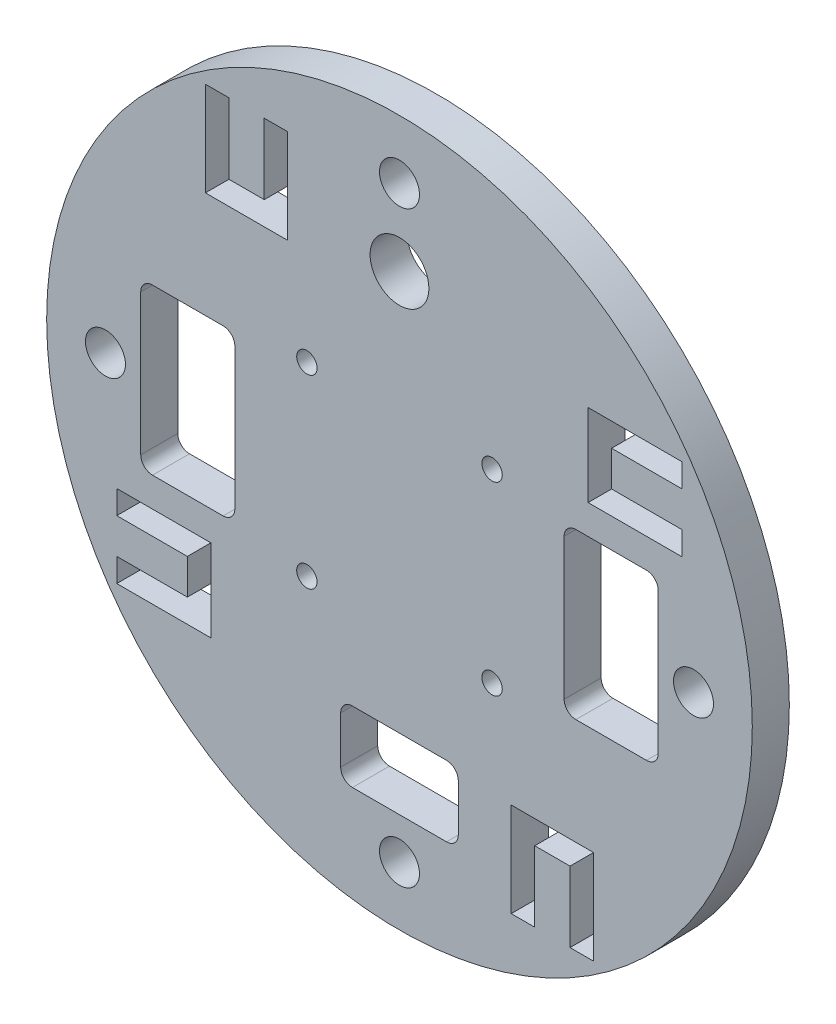
SolidWorks part; units mm, degrees
material "Hexcel AS4C (3000 Filaments)"
ref_plane "Front Plane" through (0, 0, 0) normal (0, 0, 1) x (1, 0, 0)
ref_plane "Top Plane" through (0, 0, 0) normal (0, 1, 0) x (1, 0, 0)
ref_plane "Right Plane" through (0, 0, 0) normal (1, 0, 0) x (0, 0, -1)
sketch "Sketch1" plane through (0, 0, 0) normal (0, 0, 1) x (1, 0, 0)
  circle A0 centre (0, 0) radius 38.1
  dimension "D1" = 76.2
extrude "Boss-Extrude1" add sketch "Sketch1" along normal blind 4 contours A0
sketch "Sketch2" plane through (0, 0, 4) normal (0, 0, 1) x (1, 0, 0)
  circle A0 centre (10, 10) radius 1.1
  circle A1 centre (10, -10) radius 1.1
  circle A2 centre (-10, -10) radius 1.1
  circle A3 centre (-10, 10) radius 1.1
  point P12 (0, 0)
  point P21 (0, 0)
  dimension "D3" = 2.2
  dimension "D1" = 10
  dimension "D2" = 10
  dimension "D4" = 4
extrude "Cut-Extrude1" cut sketch "Sketch2" against normal through all
sketch "Sketch3" plane through (0, 0, 4) normal (0, 0, 1) x (1, 0, 0)
  circle A0 centre (0, -31.75) radius 2.159
  circle A1 centre (-31.75, 0) radius 2.159
  circle A2 centre (0, 31.75) radius 2.159
  circle A3 centre (31.75, 0) radius 2.159
  point P9 (0, 0)
  dimension "D2" = 4.318
  dimension "D1" = 31.75
  dimension "D3" = 4
extrude "Cut-Extrude2" cut sketch "Sketch3" against normal through all both and the other way through all
sketch "Sketch4" plane through (0, 0, 4) normal (0, 0, 1) x (1, 0, 0)
  line L0 (-19.05, -8.89) -> (-26.67, -8.89)
  line L1 (19.05, 8.89) -> (26.67, 8.89)
  line L2 (17.78, 7.62) -> (17.78, -7.62)
  line L3 (19.05, -8.89) -> (26.67, -8.89)
  line L4 (27.94, 7.62) -> (27.94, -7.62)
  line L5 (-17.78, -7.62) -> (-17.78, 7.62)
  line L6 (-19.05, 8.89) -> (-26.67, 8.89)
  line L7 (-27.94, -7.62) -> (-27.94, 7.62)
  arc A0 (17.78, -7.62) -> (19.05, -8.89) centre (19.05, -7.62) ccw
  arc A1 (26.67, -8.89) -> (27.94, -7.62) centre (26.67, -7.62) ccw
  arc A2 (26.67, 8.89) -> (27.94, 7.62) centre (26.67, 7.62) cw
  arc A3 (19.05, 8.89) -> (17.78, 7.62) centre (19.05, 7.62) ccw
  arc A4 (-17.78, 7.62) -> (-19.05, 8.89) centre (-19.05, 7.62) ccw
  arc A5 (-26.67, 8.89) -> (-27.94, 7.62) centre (-26.67, 7.62) ccw
  arc A6 (-26.67, -8.89) -> (-27.94, -7.62) centre (-26.67, -7.62) cw
  arc A7 (-19.05, -8.89) -> (-17.78, -7.62) centre (-19.05, -7.62) ccw
  point P4 (17.78, 0)
  point P8 (17.78, -8.89)
  point P15 (17.78, 8.89)
  point P30 (0, 0)
  point P32 (-17.78, 0)
  dimension "D4" = 1.27
  dimension "D1" = 10.16
  dimension "D2" = 17.78
  dimension "D3" = 17.78
  dimension "D5" = 2
extrude "Cut-Extrude3" cut sketch "Sketch4" against normal through all both and the other way through all
sketch "Sketch5" plane through (0, 0, 4) normal (0, 0, 1) x (1, 0, 0)
  line L0 (0, 23.495) -> (0, -23.495) construction
  line L2 (-5.08, -27.305) -> (5.08, -27.305)
  line L3 (-6.35, -26.035) -> (-6.35, -20.955)
  line L4 (-5.08, -19.685) -> (5.08, -19.685)
  line L5 (6.35, -26.035) -> (6.35, -20.955)
  line L6 (-6.35, -27.305) -> (6.35, -19.685) construction
  line L7 (-6.35, -19.685) -> (6.35, -27.305) construction
  circle A0 centre (0, 23.495) radius 3.175
  arc A1 (-6.35, -20.955) -> (-5.08, -19.685) centre (-5.08, -20.955) cw
  arc A2 (-5.08, -27.305) -> (-6.35, -26.035) centre (-5.08, -26.035) cw
  arc A3 (5.08, -27.305) -> (6.35, -26.035) centre (5.08, -26.035) ccw
  arc A4 (5.08, -19.685) -> (6.35, -20.955) centre (5.08, -20.955) cw
  point P4 (0, 0)
  dimension "D2" = 6.35
  dimension "D5" = 1.27
  dimension "D1" = 46.99
  dimension "D3" = 12.7
  dimension "D4" = 7.62
extrude "Cut-Extrude4" cut sketch "Sketch5" against normal up to next
sketch "Sketch6" plane through (0, 0, 4) normal (0, 0, 1) x (1, 0, 0)
  line L1 (-19.05, 38.147) -> (-13.97, 38.147) construction
  line L2 (-19.05, 38.147) -> (-19.05, 30.527) construction
  line L3 (-19.05, 30.527) -> (-13.97, 30.527) construction
  line L4 (-13.97, 38.147) -> (-13.97, 30.527) construction
  line L5 (-19.05, 38.147) -> (-13.97, 30.527) construction
  line L6 (-19.05, 30.527) -> (-13.97, 38.147) construction
  line L8 (-18.415, 22.907) -> (-14.605, 22.907)
  line L11 (-12.065, 30.527) -> (-12.065, 20.367)
  line L12 (-12.065, 20.367) -> (-20.955, 20.367)
  line L13 (-20.955, 20.367) -> (-20.955, 30.527)
  line L14 (-18.415, 22.907) -> (-18.415, 30.527)
  line L15 (-18.415, 30.527) -> (-20.955, 30.527)
  line L16 (-14.605, 22.907) -> (-14.605, 30.527)
  line L17 (-14.605, 30.527) -> (-12.065, 30.527)
  line L18 (22.907, 18.415) -> (22.907, 14.605)
  line L19 (30.527, 12.065) -> (20.367, 12.065)
  line L20 (20.367, 12.065) -> (20.367, 20.955)
  line L21 (20.367, 20.955) -> (30.527, 20.955)
  line L22 (22.907, 18.415) -> (30.527, 18.415)
  line L23 (30.527, 18.415) -> (30.527, 20.955)
  line L24 (22.907, 14.605) -> (30.527, 14.605)
  line L25 (30.527, 14.605) -> (30.527, 12.065)
  line L26 (38.147, 19.05) -> (38.147, 13.97) construction
  line L27 (38.147, 19.05) -> (30.527, 19.05) construction
  line L28 (30.527, 19.05) -> (30.527, 13.97) construction
  line L29 (38.147, 13.97) -> (30.527, 13.97) construction
  line L30 (38.147, 19.05) -> (30.527, 13.97) construction
  line L31 (30.527, 19.05) -> (38.147, 13.97) construction
  line L32 (18.415, -22.907) -> (14.605, -22.907)
  line L33 (12.065, -30.527) -> (12.065, -20.367)
  line L34 (12.065, -20.367) -> (20.955, -20.367)
  line L35 (20.955, -20.367) -> (20.955, -30.527)
  line L36 (18.415, -22.907) -> (18.415, -30.527)
  line L37 (18.415, -30.527) -> (20.955, -30.527)
  line L38 (14.605, -22.907) -> (14.605, -30.527)
  line L39 (14.605, -30.527) -> (12.065, -30.527)
  line L40 (19.05, -38.147) -> (13.97, -38.147) construction
  line L41 (19.05, -38.147) -> (19.05, -30.527) construction
  line L42 (19.05, -30.527) -> (13.97, -30.527) construction
  line L43 (13.97, -38.147) -> (13.97, -30.527) construction
  line L44 (19.05, -38.147) -> (13.97, -30.527) construction
  line L45 (19.05, -30.527) -> (13.97, -38.147) construction
  line L46 (-22.907, -18.415) -> (-22.907, -14.605)
  line L47 (-30.527, -12.065) -> (-20.367, -12.065)
  line L48 (-20.367, -12.065) -> (-20.367, -20.955)
  line L49 (-20.367, -20.955) -> (-30.527, -20.955)
  line L50 (-22.907, -18.415) -> (-30.527, -18.415)
  line L51 (-30.527, -18.415) -> (-30.527, -20.955)
  line L52 (-22.907, -14.605) -> (-30.527, -14.605)
  line L53 (-30.527, -14.605) -> (-30.527, -12.065)
  line L54 (-38.147, -19.05) -> (-38.147, -13.97) construction
  line L55 (-38.147, -19.05) -> (-30.527, -19.05) construction
  line L56 (-30.527, -19.05) -> (-30.527, -13.97) construction
  line L57 (-38.147, -13.97) -> (-30.527, -13.97) construction
  line L58 (-38.147, -19.05) -> (-30.527, -13.97) construction
  line L59 (-30.527, -19.05) -> (-38.147, -13.97) construction
  circle A1 centre (0, 0) radius 38.1 construction
  circle A2 centre (0, 31.75) radius 2.159 construction
  point P0 (-16.51, 34.337)
  point P14 (-16.51, 22.907)
  point P21 (34.337, 16.51)
  point P34 (16.51, -34.337)
  point P47 (-34.337, -16.51)
  point P60 (0, 0)
  dimension "D1" = 13.97
  dimension "D2" = 5.08
  dimension "D3" = 3.81
  dimension "D4" = 2.54
  dimension "D5" = 2.54
  dimension "D6" = 7.62
  dimension "D7" = 2.54
  dimension "D8" = 7.62
  dimension "D9" = 4
extrude "Cut-Extrude5" cut sketch "Sketch6" against normal up to next
